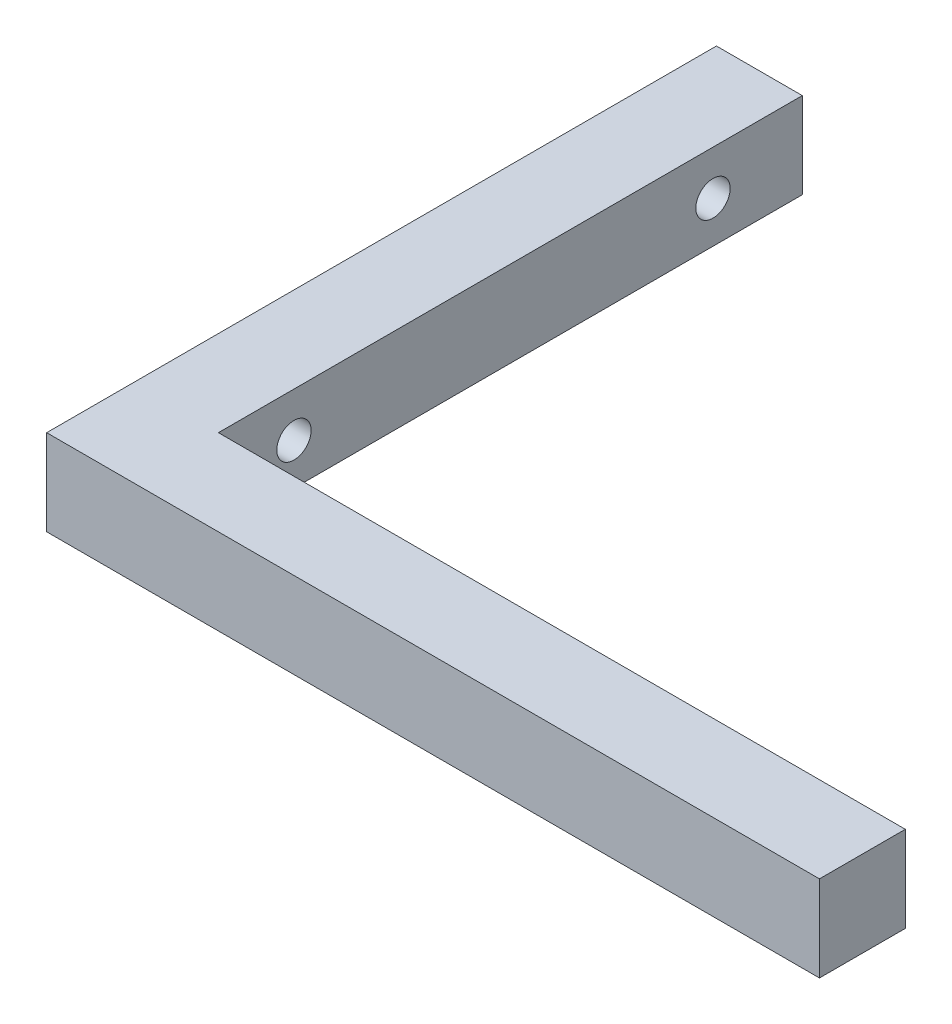
SolidWorks part; units mm, degrees
ref_plane "Front Plane" through (0, 0, 0) normal (0, 0, 1) x (1, 0, 0)
ref_plane "Top Plane" through (0, 0, 0) normal (0, 1, 0) x (1, 0, 0)
ref_plane "Right Plane" through (0, 0, 0) normal (1, 0, 0) x (0, 0, -1)
sketch "Sketch1" plane through (0, 0, 0) normal (0, 1, 0) x (1, 0, 0)
  line L0 (0, 0) -> (-57.15, 0)
  line L1 (-57.15, 0) -> (-57.15, 49.53)
  line L2 (-57.15, 49.53) -> (-50.8, 49.53)
  line L3 (-50.8, 49.53) -> (-50.8, 6.35)
  line L4 (-50.8, 6.35) -> (0, 6.35)
  line L5 (0, 6.35) -> (0, 0)
  dimension "D1" = 6.35
  dimension "D2" = 43.18
  dimension "D3" = 50.8
extrude "Boss-Extrude1" add sketch "Sketch1" along normal blind 6.35
sketch "Sketch3" plane through (-57.15, 0, 0) normal (-1, 0, 0) x (0, 0, 1)
  line L0 (-6.35, 6.35) -> (-6.35, 0)
  line L1 (-49.53, 6.35) -> (0, 6.35) construction
  line L2 (-49.53, 0) -> (0, 0) construction
  line L3 (0, 6.35) -> (0, 0) construction
  circle A0 centre (-42.926, 3.0727) radius 1.27
  circle A1 centre (-11.938, 3.0727) radius 1.27
  dimension "D2" = 2.54
  dimension "D1" = 6.35
  dimension "D3" = 5.588
  dimension "D4" = 30.988
extrude "Cut-Extrude2" cut sketch "Sketch3" against normal blind 6.35 contours A0 | A1 region at (-57.15, 3.0727, -42.926) region at (-57.15, 3.0727, -11.938)
